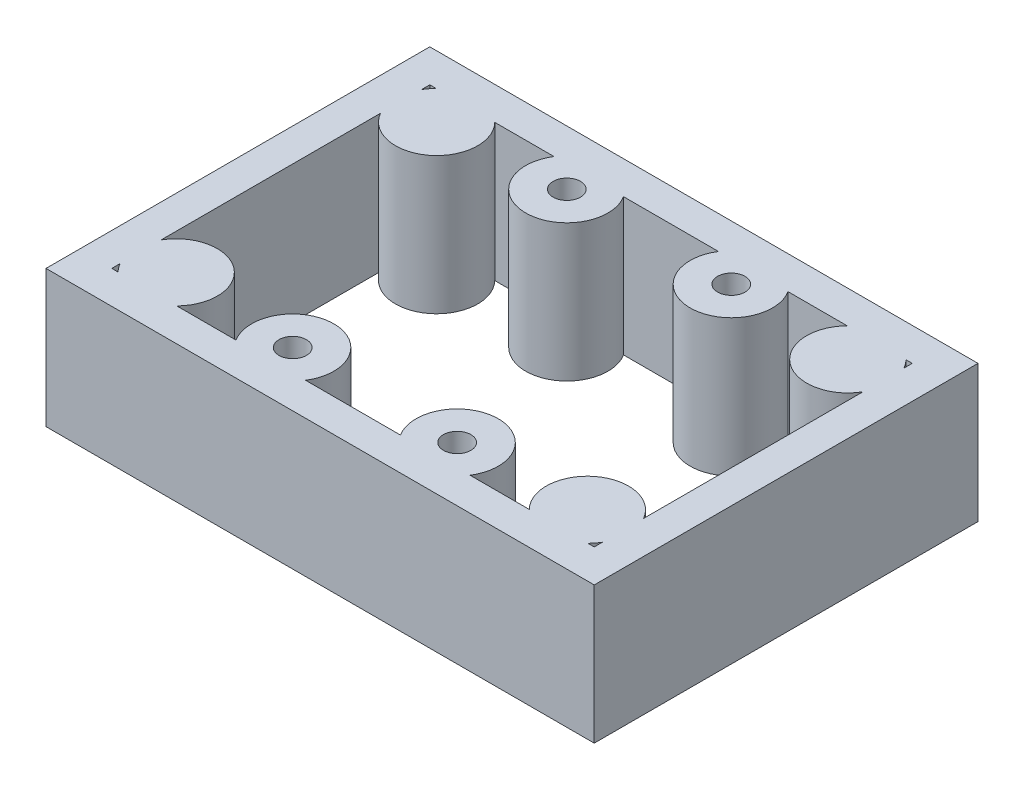
SolidWorks part; units mm, degrees
ref_plane "Front Plane" through (0, 0, 0) normal (0, 0, 1) x (1, 0, 0)
ref_plane "Top Plane" through (0, 0, 0) normal (0, 1, 0) x (1, 0, 0)
ref_plane "Right Plane" through (0, 0, 0) normal (1, 0, 0) x (0, 0, -1)
sketch "Sketch1" plane through (0, 0, 0) normal (0, 0, 1) x (1, 0, 0)
  line L1 (-20, 50) -> (20, 50)
  line L2 (-20, 50) -> (-20, 60)
  line L3 (-20, 60) -> (20, 60)
  line L4 (20, 50) -> (20, 60)
extrude "Boss-Extrude1" add sketch "Sketch1" along normal blind 28 from offset 46
sketch "Sketch2" plane through (0, 0, 0) normal (0, 0, 1) x (1, 0, 0)
  line L1 (-17.6, 49) -> (17.6, 49)
  line L2 (-17.6, 49) -> (-17.6, 61)
  line L3 (-17.6, 61) -> (17.6, 61)
  line L4 (17.6, 49) -> (17.6, 61)
extrude "Boss-Extrude2" add sketch "Sketch2" along normal blind 23.2 from offset 48.4 separate body
combine bodies "Combine1" operation type subtract main body 101 bodies to subtract 102
sketch "Sketch3" plane through (0, 0, 0) normal (0, 1, 0) x (1, 0, 0)
  circle A0 centre (-15, -50.5) radius 3
extrude "Boss-Extrude3" add sketch "Sketch3" along normal blind 10 from offset 50
sketch "Sketch4" plane through (0, 0, 0) normal (0, 1, 0) x (1, 0, 0)
  circle A0 centre (-15, -69.5) radius 3
extrude "Boss-Extrude4" add sketch "Sketch4" along normal blind 10 from offset 50
sketch "Sketch5" plane through (0, 0, 0) normal (0, 1, 0) x (1, 0, 0)
  circle A0 centre (15, -50.5) radius 3
extrude "Boss-Extrude5" add sketch "Sketch5" along normal blind 10 from offset 50
sketch "Sketch6" plane through (0, 0, 0) normal (0, 1, 0) x (1, 0, 0)
  circle A0 centre (15, -69.5) radius 3
extrude "Boss-Extrude6" add sketch "Sketch6" along normal blind 10 from offset 50
sketch "Sketch7" plane through (0, 0, 0) normal (0, 1, 0) x (1, 0, 0)
  circle A0 centre (-6, -50) radius 3
extrude "Boss-Extrude7" add sketch "Sketch7" along normal blind 10 from offset 50
sketch "Sketch8" plane through (0, 0, 0) normal (0, 1, 0) x (1, 0, 0)
  circle A0 centre (-6, -70) radius 3
extrude "Boss-Extrude8" add sketch "Sketch8" along normal blind 10 from offset 50
sketch "Sketch9" plane through (0, 0, 0) normal (0, 1, 0) x (1, 0, 0)
  circle A0 centre (6, -50) radius 3
extrude "Boss-Extrude9" add sketch "Sketch9" along normal blind 10 from offset 50
sketch "Sketch10" plane through (0, 0, 0) normal (0, 1, 0) x (1, 0, 0)
  circle A0 centre (6, -70) radius 3
extrude "Boss-Extrude10" add sketch "Sketch10" along normal blind 10 from offset 50
sketch "Sketch11" plane through (0, 0, 0) normal (0, 1, 0) x (1, 0, 0)
  circle A0 centre (-15, -50.5) radius 1
extrude "Boss-Extrude11" add sketch "Sketch11" along normal blind 9.5 from offset 49 separate body
combine bodies "Combine2" operation type subtract main body 111 bodies to subtract 112
sketch "Sketch12" plane through (0, 0, 0) normal (0, 1, 0) x (1, 0, 0)
  circle A0 centre (-15, -69.5) radius 1
extrude "Boss-Extrude12" add sketch "Sketch12" along normal blind 9.5 from offset 49 separate body
combine bodies "Combine3" operation type subtract main body 113 bodies to subtract 114
sketch "Sketch13" plane through (0, 0, 0) normal (0, 1, 0) x (1, 0, 0)
  circle A0 centre (15, -50.5) radius 1
extrude "Boss-Extrude13" add sketch "Sketch13" along normal blind 9.5 from offset 49 separate body
combine bodies "Combine4" operation type subtract main body 115 bodies to subtract 116
sketch "Sketch14" plane through (0, 0, 0) normal (0, 1, 0) x (1, 0, 0)
  circle A0 centre (15, -69.5) radius 1
extrude "Boss-Extrude14" add sketch "Sketch14" along normal blind 9.5 from offset 49 separate body
combine bodies "Combine5" operation type subtract main body 117 bodies to subtract 118
sketch "Sketch15" plane through (0, 0, 0) normal (0, 1, 0) x (1, 0, 0)
  circle A0 centre (-6, -50) radius 1
extrude "Boss-Extrude15" add sketch "Sketch15" along normal blind 9.5 from offset 51.5 separate body
combine bodies "Combine6" operation type subtract main body 119 bodies to subtract 120
sketch "Sketch16" plane through (0, 0, 0) normal (0, 1, 0) x (1, 0, 0)
  circle A0 centre (-6, -70) radius 1
extrude "Boss-Extrude16" add sketch "Sketch16" along normal blind 9.5 from offset 51.5 separate body
combine bodies "Combine7" operation type subtract main body 121 bodies to subtract 122
sketch "Sketch17" plane through (0, 0, 0) normal (0, 1, 0) x (1, 0, 0)
  circle A0 centre (6, -50) radius 1
extrude "Boss-Extrude17" add sketch "Sketch17" along normal blind 9.5 from offset 51.5 separate body
combine bodies "Combine8" operation type subtract main body 123 bodies to subtract 124
sketch "Sketch18" plane through (0, 0, 0) normal (0, 1, 0) x (1, 0, 0)
  circle A0 centre (6, -70) radius 1
extrude "Boss-Extrude18" add sketch "Sketch18" along normal blind 9.5 from offset 51.5 separate body
combine bodies "Combine9" operation type subtract main body 125 bodies to subtract 126
